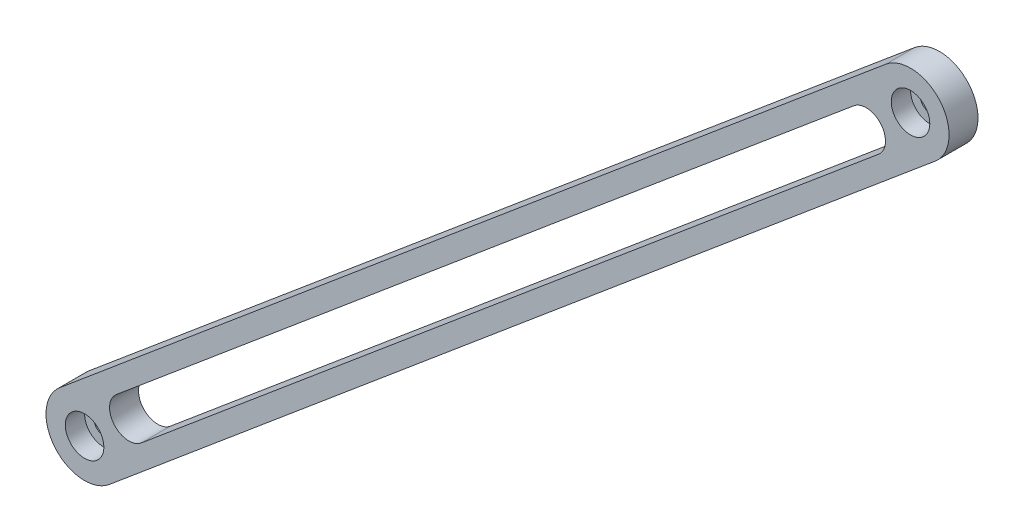
SolidWorks part; units mm, degrees
ref_plane "Front Plane" through (0, 0, 0) normal (0, 0, 1) x (1, 0, 0)
ref_plane "Top Plane" through (0, 0, 0) normal (0, 1, 0) x (1, 0, 0)
ref_plane "Right Plane" through (0, 0, 0) normal (1, 0, 0) x (0, 0, -1)
sketch "Sketch1" plane through (0, 0, 0) normal (0, 0, 1) x (1, 0, 0)
  line L0 (0, 0) -> (179.8502, 0) construction
  line L1 (8.1025, 0) -> (604.1295, 500.126) construction
  line L2 (604.1295, 500.126) -> (692.3152, 0) construction
  line L5 (568.3452, 503.2567) -> (24.3975, 46.8304)
  line L7 (600.9988, 464.3417) -> (57.0511, 7.9154)
  line L9 (555.4857, 459.309) -> (69.9106, 51.8631) construction
  line L10 (563.6491, 449.5802) -> (78.074, 42.1343)
  line L11 (547.3223, 469.0378) -> (61.7472, 61.5919)
  line L12 (40.7243, 27.3729) -> (24.3975, 46.8304) construction
  line L13 (40.7243, 27.3729) -> (57.0511, 7.9154) construction
  line L14 (568.3452, 503.2567) -> (600.9988, 464.3417) construction
  arc A0 (563.6491, 449.5802) -> (547.3223, 469.0378) centre (555.4857, 459.309) ccw
  arc A1 (61.7472, 61.5919) -> (78.074, 42.1343) centre (69.9106, 51.8631) ccw
  circle A2 centre (40.7243, 27.3729) radius 6.35
  arc A3 (24.3975, 46.8304) -> (57.0511, 7.9154) centre (40.7243, 27.3729) ccw
  circle A4 centre (584.672, 483.7992) radius 6.35
  arc A5 (568.3452, 503.2567) -> (600.9988, 464.3417) centre (584.672, 483.7992) cw
  point P6 (604.1295, 500.126)
  point P12 (312.6981, 255.586)
  point P24 (584.672, 483.7992)
  point P25 (603.2334, 499.3741)
  dimension "D6" = 12.7
  dimension "D7" = 12.7
  dimension "D4" = 25.4
  dimension "D3" = 25.4
  dimension "D1" = 40
  dimension "D2" = 80
  dimension "D5" = 500.126
  dimension "D8" = 38.1
  dimension "D9" = 38.1
extrude "Boss-Extrude1" add sketch "Sketch1" along normal blind 19.05
sketch "Sketch2" plane through (0, 0, 19.05) normal (0, 0, 1) x (1, 0, 0)
  circle A0 centre (40.7243, 27.3729) radius 12.7
  circle A1 centre (584.672, 483.7992) radius 12.7
  dimension "D1" = 25.4
extrude "Cut-Extrude1" cut sketch "Sketch2" against normal blind 12.7
